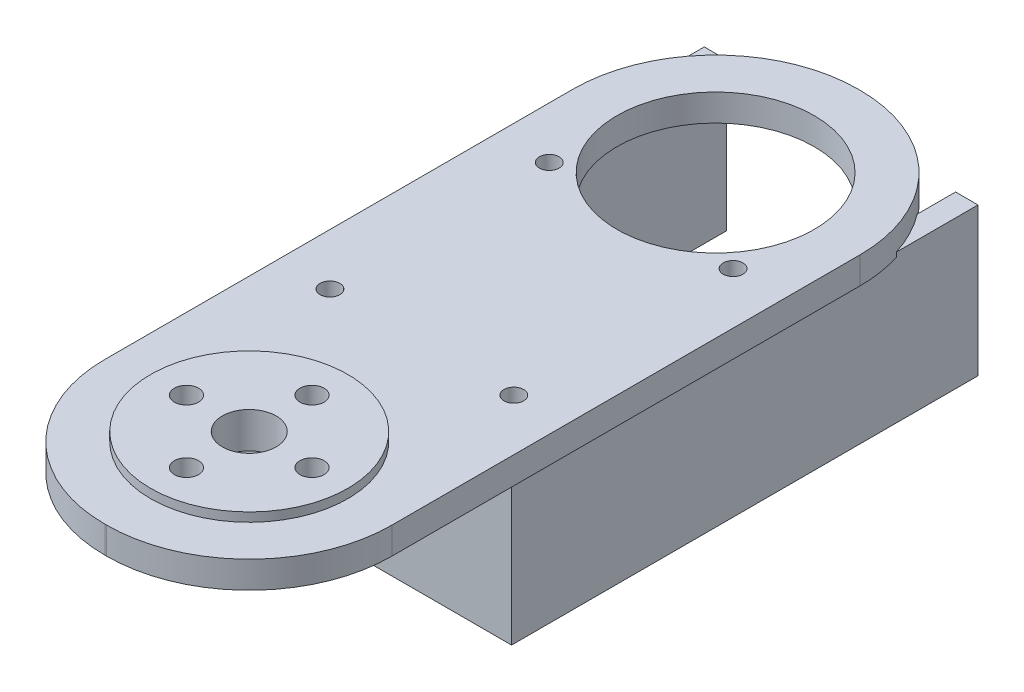
SolidWorks part; units mm, degrees
ref_plane "Front Plane" through (0, 0, 0) normal (0, 0, 1) x (1, 0, 0)
ref_plane "Top Plane" through (0, 0, 0) normal (0, 1, 0) x (1, 0, 0)
ref_plane "Right Plane" through (0, 0, 0) normal (1, 0, 0) x (0, 0, -1)
ref_plane "PY_m1_100" through (0, -1.1, 0) normal (0, 1, 0) x (1, 0, 0)
sketch "S_cyl1" plane through (0, -1.1, 0) normal (0, 1, 0) x (1, 0, 0)
  circle A0 centre (0, 0) radius 11
  dimension "D1_S_cyl1" = 22
extrude "Boss_1" add sketch "S_cyl1" along normal blind 1.1
ref_plane "PY_m4_000" through (0, -4, 0) normal (0, 1, 0) x (1, 0, 0)
sketch "S_prism2" plane through (0, -4, 0) normal (0, 1, 0) x (1, 0, 0)
  line L0 (-0.1, -16) -> (0.1, -16)
  line L1 (16, -0.1) -> (16, 52.1)
  line L2 (0.1, 68) -> (-0.1, 68)
  line L3 (-16, 52.1) -> (-16, -0.1)
  arc A0 (-16, -0.1) -> (-0.1, -16) centre (-0.1, -0.1) ccw
  arc A1 (0.1, -16) -> (16, -0.1) centre (0.1, -0.1) ccw
  arc A2 (16, 52.1) -> (0.1, 68) centre (0.1, 52.1) ccw
  arc A3 (-0.1, 68) -> (-16, 52.1) centre (-0.1, 52.1) ccw
extrude "Boss_2" add sketch "S_prism2" along normal blind 3
ref_plane "PZ_m66_000" through (0, 0, -66) normal (0, 0, 1) x (1, 0, 0)
sketch "S_box3" plane through (0, 0, -66) normal (0, 0, 1) x (1, 0, 0)
  line L0 (12.76, -20) -> (15.26, -20)
  line L1 (15.26, -20) -> (15.26, -3.5)
  line L2 (15.26, -3.5) -> (12.76, -3.5)
  line L3 (12.76, -3.5) -> (12.76, -20)
  dimension "P1" = 12.76
  dimension "P2" = 20
  dimension "P3" = 15.26
  dimension "P4" = 20
  dimension "P5" = 15.26
  dimension "P6" = 3.5
  dimension "P7" = 12.76
  dimension "P8" = 3.5
extrude "Boss_3" add sketch "S_box3" along normal blind 52.01
sketch "S_box4" plane through (0, 0, -66) normal (0, 0, 1) x (1, 0, 0)
  line L0 (-15.26, -20) -> (-12.76, -20)
  line L1 (-12.76, -20) -> (-12.76, -3.5)
  line L2 (-12.76, -3.5) -> (-15.26, -3.5)
  line L3 (-15.26, -3.5) -> (-15.26, -20)
  dimension "P1" = 15.26
  dimension "P2" = 20
  dimension "P3" = 12.76
  dimension "P4" = 20
  dimension "P5" = 12.76
  dimension "P6" = 3.5
  dimension "P7" = 15.26
  dimension "P8" = 3.5
extrude "Boss_4" add sketch "S_box4" along normal blind 52.01
ref_plane "PZ_m16_490" through (0, 0, -16.49) normal (0, 0, 1) x (1, 0, 0)
sketch "S_box5" plane through (0, 0, -16.49) normal (0, 0, 1) x (1, 0, 0)
  line L0 (-15.26, -20) -> (15.26, -20)
  line L1 (15.26, -20) -> (15.26, -3.5)
  line L2 (15.26, -3.5) -> (-15.26, -3.5)
  line L3 (-15.26, -3.5) -> (-15.26, -20)
  dimension "P1" = 15.26
  dimension "P2" = 20
  dimension "P3" = 15.26
  dimension "P4" = 20
  dimension "P5" = 15.26
  dimension "P6" = 3.5
  dimension "P7" = 15.26
  dimension "P8" = 3.5
extrude "Boss_5" add sketch "S_box5" along normal blind 2.5
ref_plane "PY_m4_100" through (0, -4.1, 0) normal (0, 1, 0) x (1, 0, 0)
sketch "S_hole6" plane through (0, -4.1, 0) normal (0, 1, 0) x (1, 0, 0)
  circle A0 centre (0, 0) radius 3
  dimension "D1_S_hole6" = 6
extrude "Hole_6" cut sketch "S_hole6" along normal blind 4.2
sketch "S_hole7" plane through (0, -4.1, 0) normal (0, 1, 0) x (1, 0, 0)
  circle A0 centre (7, 0) radius 1.35
  dimension "D1_S_hole7" = 2.7
  dimension "P2" = 7
extrude "Hole_7" cut sketch "S_hole7" along normal blind 4.2
sketch "S_hole8" plane through (0, -4.1, 0) normal (0, 1, 0) x (1, 0, 0)
  circle A0 centre (0, -7) radius 1.35
  dimension "D1_S_hole8" = 2.7
  dimension "P2" = 7
extrude "Hole_8" cut sketch "S_hole8" along normal blind 4.2
sketch "S_hole9" plane through (0, -4.1, 0) normal (0, 1, 0) x (1, 0, 0)
  circle A0 centre (-7, 0) radius 1.35
  dimension "D1_S_hole9" = 2.7
  dimension "P2" = 7
extrude "Hole_9" cut sketch "S_hole9" along normal blind 4.2
sketch "S_hole10" plane through (0, -4.1, 0) normal (0, 1, 0) x (1, 0, 0)
  circle A0 centre (0, 7) radius 1.35
  dimension "D1_S_hole10" = 2.7
  dimension "P2" = 7
extrude "Hole_10" cut sketch "S_hole10" along normal blind 4.2
sketch "S_hole11" plane through (0, -4.1, 0) normal (0, 1, 0) x (1, 0, 0)
  circle A0 centre (0, 52) radius 11
  dimension "D1_S_hole11" = 22
  dimension "P2" = 52
extrude "Hole_11" cut sketch "S_hole11" along normal blind 3.2
sketch "S_hole12" plane through (0, -4.1, 0) normal (0, 1, 0) x (1, 0, 0)
  circle A0 centre (-10.25, 43.7) radius 1.1
  dimension "D1_S_hole12" = 2.2
  dimension "P2" = 10.25
  dimension "P3" = 43.7
extrude "Hole_12" cut sketch "S_hole12" along normal blind 3.2
sketch "S_hole13" plane through (0, -4.1, 0) normal (0, 1, 0) x (1, 0, 0)
  circle A0 centre (10.25, 43.7) radius 1.1
  dimension "D1_S_hole13" = 2.2
  dimension "P2" = 10.25
  dimension "P3" = 43.7
extrude "Hole_13" cut sketch "S_hole13" along normal blind 3.2
sketch "S_hole14" plane through (0, -4.1, 0) normal (0, 1, 0) x (1, 0, 0)
  circle A0 centre (-10.25, 19.25) radius 1.1
  dimension "D1_S_hole14" = 2.2
  dimension "P2" = 10.25
  dimension "P3" = 19.25
extrude "Hole_14" cut sketch "S_hole14" along normal blind 3.2
sketch "S_hole15" plane through (0, -4.1, 0) normal (0, 1, 0) x (1, 0, 0)
  circle A0 centre (10.25, 19.25) radius 1.1
  dimension "D1_S_hole15" = 2.2
  dimension "P2" = 10.25
  dimension "P3" = 19.25
extrude "Hole_15" cut sketch "S_hole15" along normal blind 3.2
equation "\"plate_t\" = 3"
equation "\"clearance\" = 0.4"
